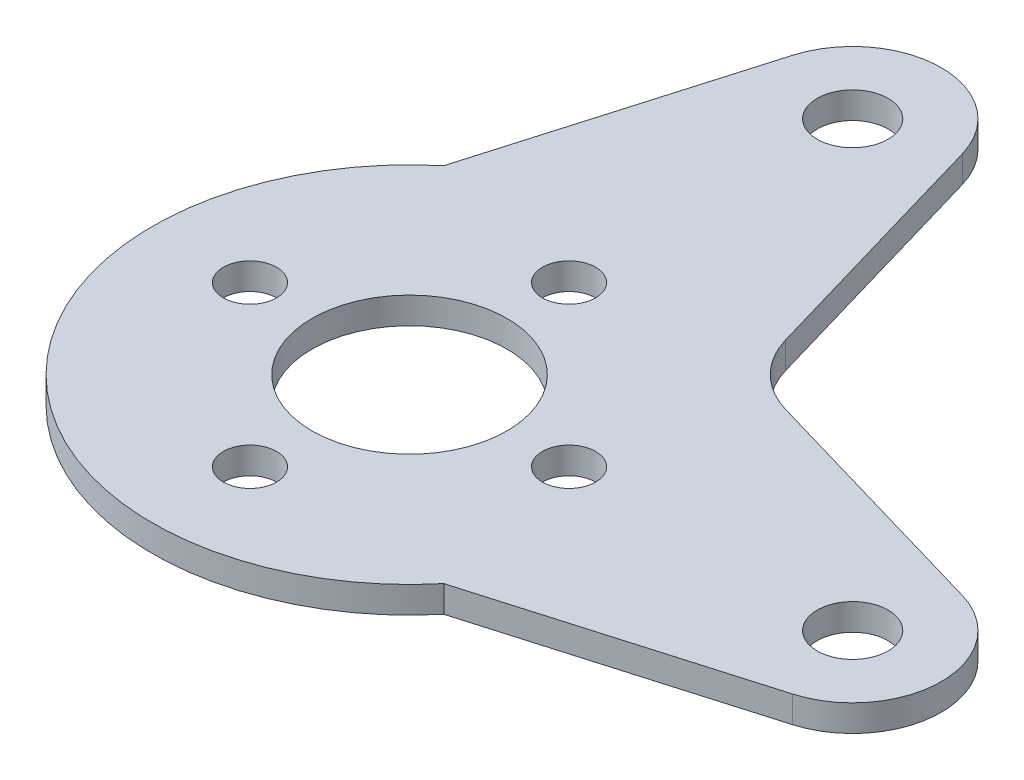
SolidWorks part; units mm, degrees
material "ABS PC"
ref_plane "Płaszczyzna przednia" through (0, 0, 0) normal (0, 0, 1) x (1, 0, 0)
ref_plane "Płaszczyzna górna" through (0, 0, 0) normal (0, 1, 0) x (1, 0, 0)
ref_plane "Płaszczyzna prawa" through (0, 0, 0) normal (1, 0, 0) x (0, 0, -1)
sketch "Szkic1" plane through (0, 0, 0) normal (0, 1, 0) x (1, 0, 0)
  line L0 (22.3477, -18.4819) -> (52.8, -9.6)
  line L1 (24.6194, 17.8194) -> (52.8, 9.6)
  line L2 (17.8194, 24.6194) -> (9.6, 52.8)
  line L3 (-18.4819, 22.3477) -> (-9.6, 52.8)
  circle A0 centre (0, 0) radius 11
  circle A1 centre (18, 0) radius 3
  arc A2 (52.8, -9.6) -> (52.8, 9.6) centre (50, 0) ccw
  arc A3 (17.8194, 24.6194) -> (24.6194, 17.8194) centre (27.4194, 27.4194) ccw
  circle A4 centre (50, 0) radius 4
  arc A5 (-18.4819, 22.3477) -> (22.3477, -18.4819) centre (0, 0) ccw
  arc A6 (9.6, 52.8) -> (-9.6, 52.8) centre (0, 50) ccw
  circle A7 centre (0, 50) radius 4
  circle A8 centre (-18, 0) radius 3
  circle A9 centre (0, -18) radius 3
  circle A10 centre (0, 18) radius 3
extrude "Dodanie-wyciągnięcie1" add sketch "Szkic1" along normal blind 3
